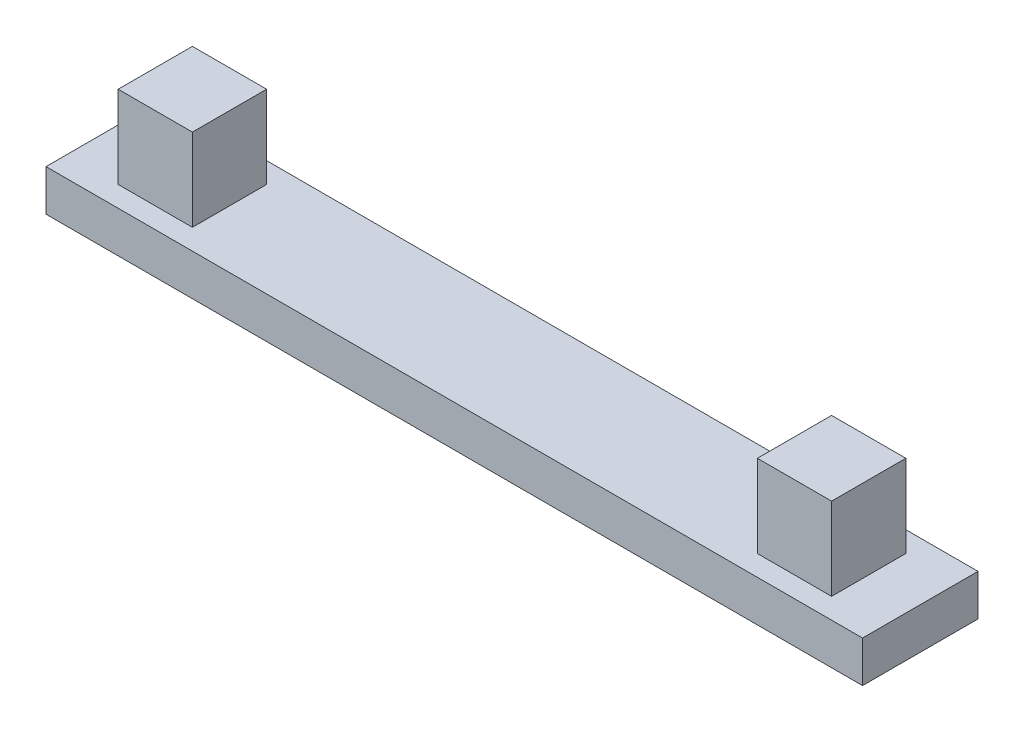
SolidWorks part; units mm, degrees
ref_plane "Front Plane" through (0, 0, 0) normal (0, 0, 1) x (1, 0, 0)
ref_plane "Top Plane" through (0, 0, 0) normal (0, 1, 0) x (1, 0, 0)
ref_plane "Right Plane" through (0, 0, 0) normal (1, 0, 0) x (0, 0, -1)
sketch "Sketch1" plane through (0, 0, 0) normal (0, 1, 0) x (1, 0, 0)
  line L1 (0, 0) -> (19.8, 0)
  line L2 (0, 0) -> (0, 2.8)
  line L3 (0, 2.8) -> (19.8, 2.8)
  line L4 (19.8, 0) -> (19.8, 2.8)
  line L5 (0, 0) -> (19.8, 2.8) construction
  line L6 (0, 2.8) -> (19.8, 0) construction
  line L7 (1.25, 2.3) -> (3.05, 2.3)
  line L8 (1.25, 2.3) -> (1.25, 0.5)
  line L9 (1.25, 0.5) -> (3.05, 0.5)
  line L10 (3.05, 2.3) -> (3.05, 0.5)
  line L11 (1.25, 2.3) -> (3.05, 0.5) construction
  line L12 (1.25, 0.5) -> (3.05, 2.3) construction
  line L13 (16.75, 2.3) -> (18.55, 2.3)
  line L14 (16.75, 2.3) -> (16.75, 0.5)
  line L15 (16.75, 0.5) -> (18.55, 0.5)
  line L16 (18.55, 2.3) -> (18.55, 0.5)
  line L17 (16.75, 2.3) -> (18.55, 0.5) construction
  line L18 (16.75, 0.5) -> (18.55, 2.3) construction
  point P4 (9.9, 1.4)
  point P10 (2.15, 1.4)
  point P15 (17.65, 1.4)
  point P17 (0, 1.4)
  point P22 (19.8, 1.4)
  dimension "D1" = 19.8
  dimension "D2" = 2.8
  dimension "D3" = 15.5
  dimension "D4" = 1.8
  dimension "D5" = 7.75
extrude "Boss-Extrude1" add sketch "Sketch1" along normal blind 1 contours L1 L4 L3 L2 L7 L10 L9 L8 L13 L16 L15 L14 region at (9.9, 0, -1.4)
ref_plane "Plane1" through (3.05, 0, -2.3) normal (1, 0, 0) x (0, 0, -1)
extrude "Boss-Extrude2" add sketch "Sketch1<3>" along normal blind 3 contours L7 L10 L9 L8 | L13 L16 L15 L14
sketch "Sketch1<3>" plane through (0, 0, 0) normal (0, 1, 0) x (1, 0, 0) same geometry as "Sketch1"
